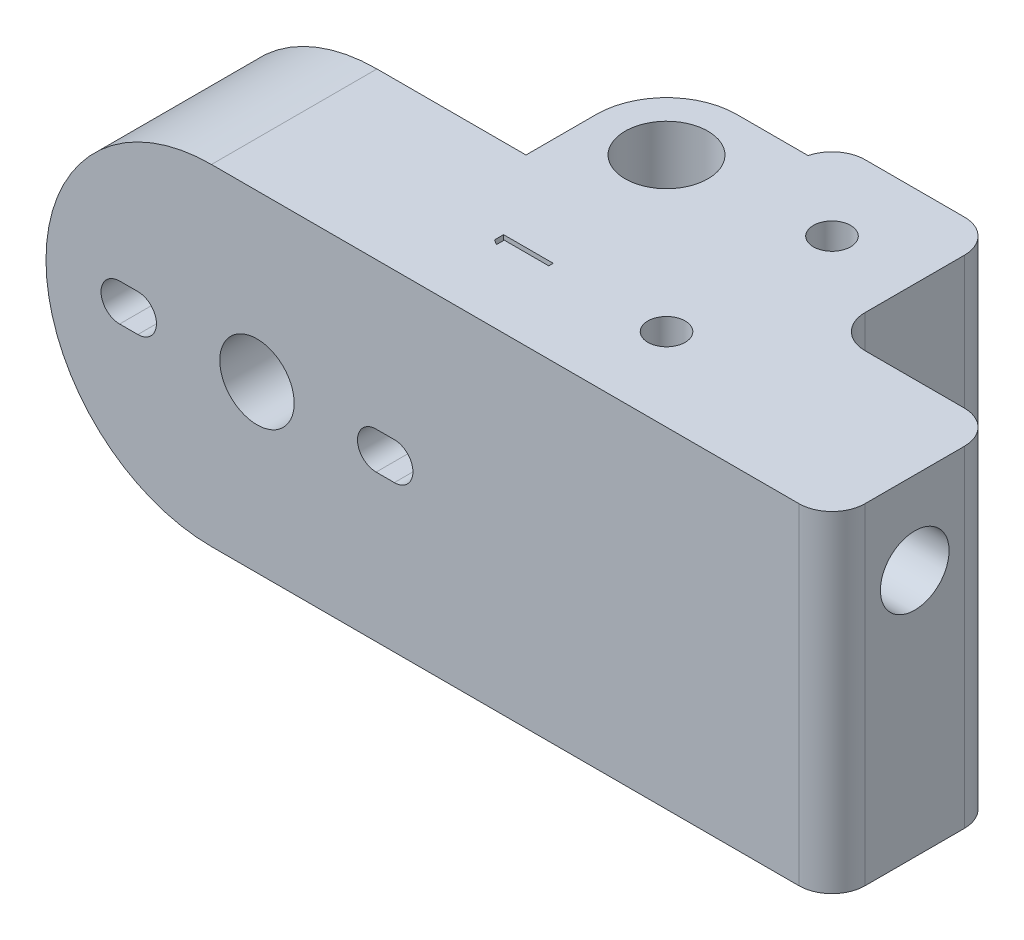
SolidWorks part; units mm, degrees
note: The reader was unsure of these and kept them because the rebuilt part matched: shared geometry of "Croquis9<4>".
ref_plane "Alzado" through (0, 0, 0) normal (0, 0, 1) x (1, 0, 0)
ref_plane "Planta" through (0, 0, 0) normal (0, 1, 0) x (1, 0, 0)
ref_plane "Vista lateral" through (0, 0, 0) normal (1, 0, 0) x (0, 0, -1)
sketch "Croquis1" plane through (0, 0, 0) normal (0, 1, 0) x (1, 0, 0)
  line L0 (0, 0) -> (40, 0)
  line L1 (40, 0) -> (40, 20)
  line L2 (40, 20) -> (20, 20)
  line L3 (20, 20) -> (20, 40)
  line L4 (20, 40) -> (0, 40)
  line L5 (0, 40) -> (0, 0)
extrude "Saliente-Extruir1" add sketch "Croquis1" along normal blind 40
sketch "Croquis4" plane through (0, 40, 0) normal (0, 1, 0) x (1, 0, 0)
  line L0 (10, 30) -> (10, 10) construction
  circle A0 centre (10, 30) radius 2.25
  circle A1 centre (10, 10) radius 2.25
extrude "Cortar-Extruir3" cut sketch "Croquis4" against normal through all
sketch "Croquis5" plane through (0, 0, 0) normal (0, 0, 1) x (1, 0, 0)
  line L3 (0, 40) -> (-35, 40)
  line L4 (0, 0) -> (-35, 0)
  line L5 (0, 40) -> (0, 0)
  line L6 (0, 0) -> (0.4379, 0.1277)
  arc A1 (-35, 40) -> (-35, 0) centre (-35, 20) ccw
extrude "Saliente-Extruir2" add sketch "Croquis5" against normal blind 20
sketch "Croquis8" plane through (40, 0, 0) normal (1, 0, 0) x (0, 0, -1)
  line L0 (0, 0) -> (10, 0) construction
  line L1 (0, 0) -> (20, 0) construction
  line L2 (10, 0) -> (10, 30) construction
  circle A0 centre (10, 30) radius 4.15
extrude "Cortar-Extruir4" cut sketch "Croquis8" against normal blind 25
sketch "Croquis9" plane through (0, 0, -20) normal (0, 0, -1) x (-1, 0, 0)
  line L0 (10.9783, 25.4724) -> (25.756, 30.6617)
  line L1 (35, 0) -> (35, 40) construction
  line L2 (10.9783, 14.5276) -> (25.756, 9.3383)
  line L3 (12.9, 22.25) -> (15.1, 22.25)
  line L4 (43.9, 17.75) -> (46.1, 17.75)
  line L5 (46.1, 22.25) -> (43.9, 22.25)
  line L6 (33.244, 30.6617) -> (48.0217, 25.4724)
  line L7 (15.1, 17.75) -> (12.9, 17.75)
  line L8 (33.244, 9.3383) -> (48.0217, 14.5276)
  arc A0 (35, 0) -> (35, 40) centre (35, 20) ccw construction
  circle A1 centre (29.5, 20) radius 4.5
  arc A2 (12.9, 17.75) -> (12.9, 22.25) centre (12.9, 20) cw
  arc A3 (43.9, 22.25) -> (43.9, 17.75) centre (43.9, 20) ccw
  arc A4 (46.1, 17.75) -> (46.1, 22.25) centre (46.1, 20) ccw
  arc A5 (15.1, 22.25) -> (15.1, 17.75) centre (15.1, 20) cw
  arc A6 (25.756, 9.3383) -> (33.244, 9.3383) centre (29.5, 20) ccw
  arc A7 (33.244, 30.6617) -> (25.756, 30.6617) centre (29.5, 20) ccw
  arc A9 (10.9783, 25.4724) -> (10.9783, 14.5276) centre (12.9, 20) ccw
  arc A10 (48.0217, 14.5276) -> (48.0217, 25.4724) centre (46.1, 20) ccw
extrude "Cortar-Extruir6" cut sketch "Croquis9" against normal blind 20 contours L4 A4 L5 A3 | A1 | A5 L7 A2 L3
extrude "Cortar-Extruir7" cut sketch "Croquis9<4>" against normal blind 5.5
sketch "Croquis9<4>" plane through (0, 0, -20) normal (0, 0, -1) x (-1, 0, 0) same geometry as "Croquis9"
fillet "Redondeo3" radius 4 6 edges at (40, 20, 0) (40, 20, -20) (20, 20, -20) (20, 20, -40) (0, 20, -40) (0, 20, -20)
sketch "Croquis10" plane through (0, 40, 0) normal (0, 1, 0) x (1, 0, 0)
  line L0 (-4, 20) -> (-4, 0) construction
  line L1 (-35, 0) -> (36, 0) construction
  text T0 "1" font "Century Gothic" height 6
extrude "Cortar-Extruir8" cut sketch "Croquis10" against normal blind 1
sketch "Croquis11" plane through (0, 40, 0) normal (0, 1, 0) x (1, 0, 0)
  line L0 (-16.985, 28.4925) -> (-16.985, 20)
  line L2 (-4, 20) -> (-35, 20) construction
  line L3 (-8.4925, 36.985) -> (0.1232, 36.985)
  line L5 (-16.985, 20) -> (-4, 20)
  line L6 (-14.4976, 34.4976) -> (-15.8135, 35.8135) construction
  line L7 (0.1232, 36.985) -> (0, 24)
  circle A1 centre (-8.4925, 28.4925) radius 5
  arc A2 (-8.4925, 36.985) -> (-16.985, 28.4925) centre (-8.4925, 28.4925) ccw
  arc A3 (4, 40) -> (0, 36) centre (4, 36) ccw construction
  arc A4 (-4, 20) -> (0, 24) centre (-4, 24) ccw
extrude "Saliente-Extruir3" add sketch "Croquis11" against normal blind 10
